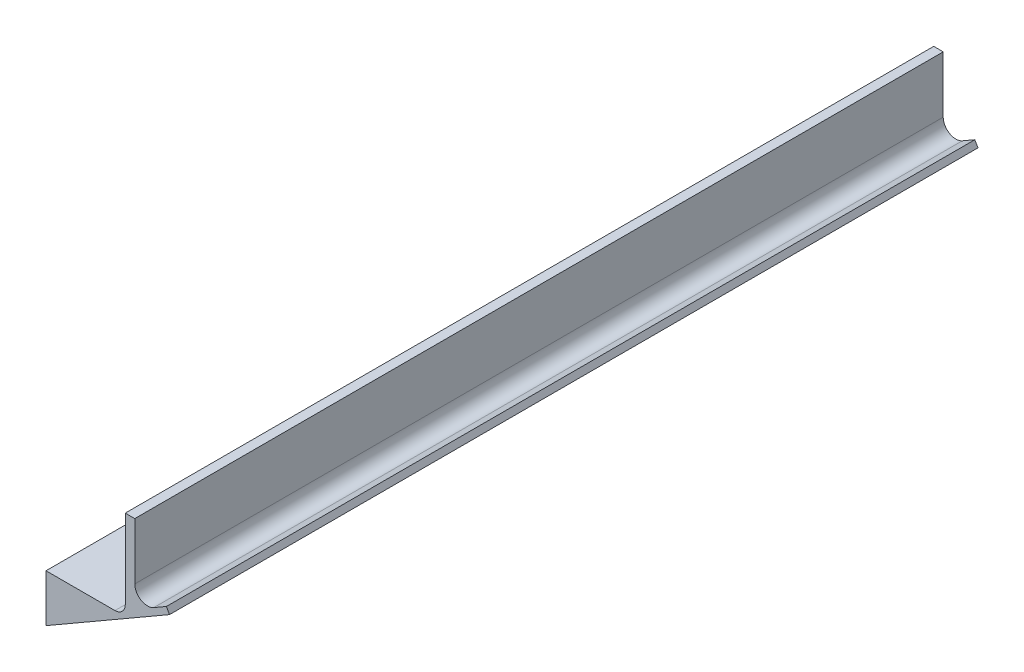
SolidWorks part; units mm, degrees
ref_plane "Alzado" through (0, 0, 0) normal (0, 0, 1) x (1, 0, 0)
ref_plane "Planta" through (0, 0, 0) normal (0, 1, 0) x (1, 0, 0)
ref_plane "Vista lateral" through (0, 0, 0) normal (1, 0, 0) x (0, 0, -1)
sketch "Croquis2" plane through (0, 0, 0) normal (0, 0, 1) x (1, 0, 0)
  line L0 (0, 0) -> (21.75, 0)
  line L1 (25, 3.25) -> (25, 28.25)
  line L4 (25, 28.25) -> (28, 28.25)
  line L5 (28, 28.25) -> (28, 10.4034)
  line L6 (0, 0) -> (0, -15)
  line L8 (38.9711, 7.5) -> (0, -15)
  line L9 (38.9711, 7.5) -> (0, 7.5) construction
  line L10 (38.9711, 7.5) -> (37.9711, 9.2321)
  line L11 (37.9711, 9.2321) -> (34, 6.9393)
  arc A0 (21.75, 0) -> (25, 3.25) centre (21.75, 3.25) ccw
  arc A1 (28, 10.4034) -> (34, 6.9393) centre (32, 10.4034) ccw
  dimension "D1" = 6.5
  dimension "D7" = 2
  dimension "D8" = 4
  dimension "D2" = 3
  dimension "D3" = 25
  dimension "D4" = 30
  dimension "D5" = 25
  dimension "D6" = 15
  dimension "D9" = 45
extrude "Saliente-Extruir1" add sketch "Croquis2" along normal blind 255
sketch "Croquis3" plane through (0, 0, 0) normal (0, 1, 0) x (1, 0, 0)
  line L0 (14.45, 0) -> (14.45, -255) construction
  line L1 (21.75, 0) -> (0, 0) construction
  line L2 (21.75, -255) -> (0, -255) construction
  line L3 (21.75, -255) -> (21.75, 0) construction
  circle A0 centre (14.45, -199) radius 3.25
  circle A1 centre (14.45, -56) radius 3.25
  point P12 (14.45, -127.5)
  dimension "D2" = 6.5
  dimension "D3" = 6.5
  dimension "D1" = 7.3
  dimension "D4" = 143
  dimension "D5" = 71.5
sketch "Croquis4" plane through (0, 0, 0) normal (-1, 0, 0) x (0, 0, 1)
  line L0 (0, -8) -> (255, -8) construction
  line L3 (255, -15) -> (0, -15) construction
  text T0 "<b>BIOBIZKAIA</b>" font "Century Gothic" height in points 28
  dimension "D1" = 7
extrude "Cortar-Extruir1" cut sketch "Croquis4" against normal blind 1
extrude "Cortar-Extruir2" cut sketch "Croquis3" against normal blind 4
